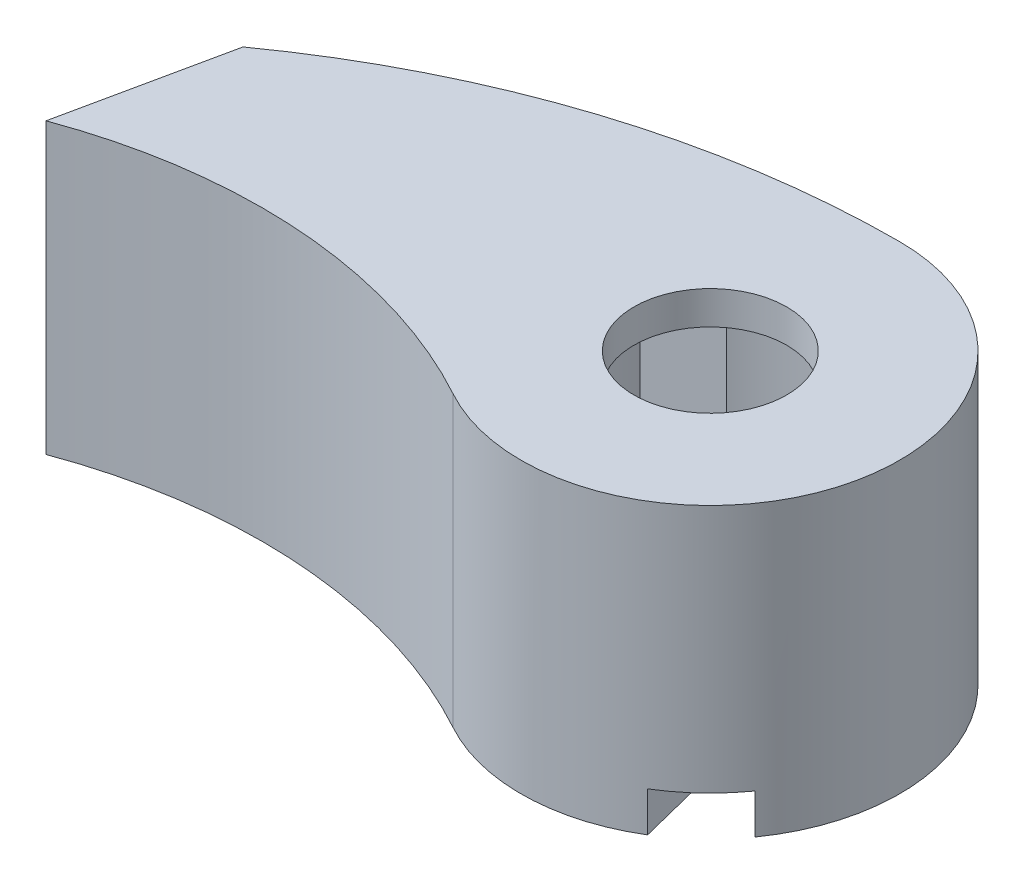
SolidWorks part; units mm, degrees
material "PLA"
ref_plane "Front Plane" through (0, 0, 0) normal (0, 0, 1) x (1, 0, 0)
ref_plane "Top Plane" through (0, 0, 0) normal (0, 1, 0) x (1, 0, 0)
ref_plane "Right Plane" through (0, 0, 0) normal (1, 0, 0) x (0, 0, -1)
sketch "Sketch1" plane through (0, 0, 0) normal (0, 1, 0) x (1, 0, 0)
  line L0 (-8, -2) -> (-7.4802, 0.4454)
  line L3 (-6.5163, 0.0837) -> (-1.1819, 1.4232)
  line L4 (-1.7251, 0.6682) -> (-6.3702, -0.4982)
  line L5 (-6.5163, 0.0837) -> (-6.3702, -0.4982)
  line L6 (-8, -1002) -> (-8, 48998) construction
  circle A0 centre (0, 0) radius 1.85 construction
  circle A1 centre (0, 0) radius 2.85 construction
  arc A3 (-8, -2) -> (-1.3741, -2.4969) centre (-5.2313, -9.5056) cw
  arc A4 (0, 2.85) -> (-1.3741, -2.4969) centre (0, 0) cw
  arc A5 (-7.4802, 0.4454) -> (0, 2.85) centre (0, -9.9869) cw
  arc A6 (-1.1819, 1.4232) -> (-1.7251, 0.6682) centre (0, 0) cw
  dimension "D1" = 0.6
  dimension "D2" = 3.7
  dimension "D3" = 8
  dimension "D4" = 8
  dimension "D9" = 12
  dimension "D8" = 1
  dimension "D5" = 2.5
  dimension "D6" = 2
  dimension "D7" = 5.5
extrude "Boss-Extrude1" add sketch "Sketch1" along normal blind 0.5 contours A3 A4 A5 L0
extrude "Boss-Extrude2" add sketch "Sketch1<3>" against normal blind 3.85
sketch "Sketch1<3>" plane through (0, 0, 0) normal (0, 1, 0) x (1, 0, 0) same geometry as "Sketch1"
sketch "Sketch2" plane through (0, 0, 0) normal (0, -1, 0) x (1, 0, 0)
  circle A0 centre (0, 0) radius 1.15
  dimension "D1" = 2.3
extrude "Cut-Extrude1" cut sketch "Sketch2" against normal blind 10
sketch "Sketch3" plane through (0, 0, 0) normal (0, -1, 0) x (1, 0, 0)
  line L0 (-6.4432, 0.2072) -> (-0.3332, -1.327) construction
  line L1 (-6.5163, -0.0837) -> (-6.3702, 0.4982) construction
  line L2 (-6.3702, 0.4982) -> (-1.7251, -0.6682) construction
  line L3 (1.327, -0.3332) -> (1.9359, 2.0916) construction
  line L4 (1.0855, 0.8329) -> (1.4869, 2.4314)
  line L5 (1.7943, -0.4506) -> (2.3223, 1.6521)
  line L7 (1.7943, -0.4506) -> (1.0855, 0.8329)
  circle A0 centre (0, 0) radius 1.3682 construction
  arc A1 (0, -2.85) -> (-1.3741, 2.4969) centre (0, 0) ccw construction
  arc A2 (-1.1819, -1.4232) -> (-1.7251, -0.6682) centre (0, 0) ccw construction
  arc A3 (1.4869, 2.4314) -> (2.3223, 1.6521) centre (0, 0) cw
  arc A4 (-1.1819, -1.4232) -> (-1.7251, -0.6682) centre (0, 0) ccw construction
  dimension "D1" = 1
extrude "Cut-Extrude2" cut sketch "Sketch3" against normal blind 0.6 from surface starting at face at (-3.2096, -3.85, 0.1123)
